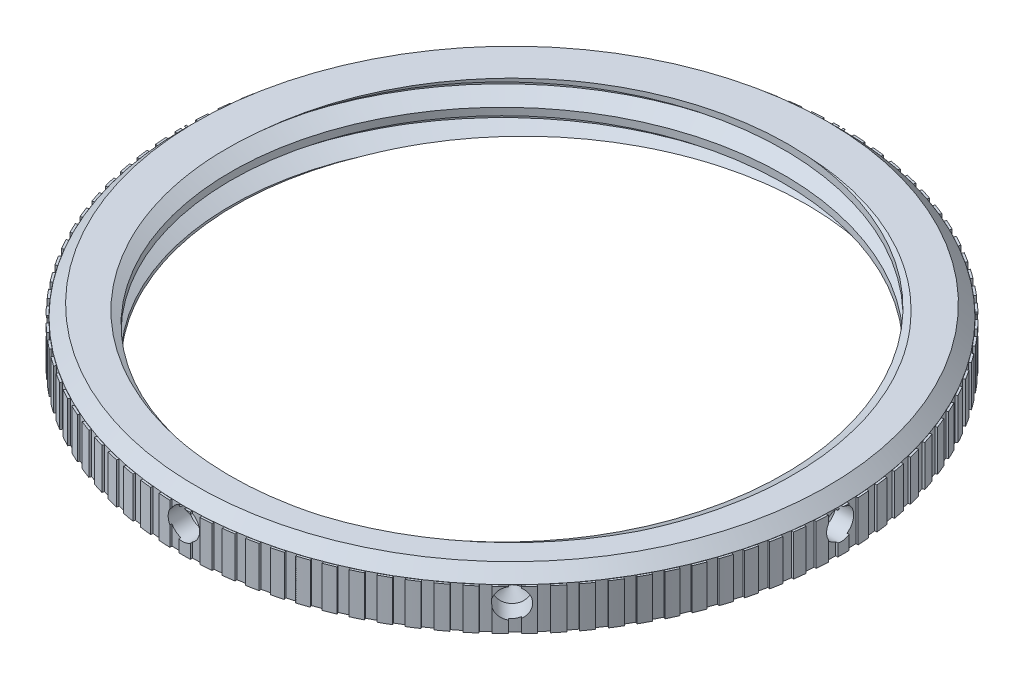
SolidWorks part; units mm, degrees
ref_plane "前视基准面" through (0, 0, 0) normal (0, 0, 1) x (1, 0, 0)
ref_plane "上视基准面" through (0, 0, 0) normal (0, 1, 0) x (1, 0, 0)
ref_plane "右视基准面" through (0, 0, 0) normal (1, 0, 0) x (0, 0, -1)
sketch "草图1" plane through (0, -4.5977, 0) normal (0, -1, 0) x (1, 0, 0)
  circle A0 centre (0, 0) radius 5
  circle A1 centre (0, 0) radius 5.6
  dimension "D1" = 10
  dimension "D2" = 11.2
extrude "凸台-拉伸1" add sketch "草图1" against normal blind 0.9 from surface at 0
chamfer "倒角2" distance 0.2 angle 45 1 edges at (0, -3.6977, -5.6)
thread "螺纹线1" pitch 0.5 start angle 0, offset 1, length 0, pitch 0.5, diameter 10
ref_plane "基准面4" through (5, -5.5977, 0) normal (0, 0, 1) x (1, 0, 0)
sketch "螺纹线轮廓1" plane through (5, -5.5977, 0) normal (0, 0, 1) x (1, 0, 0)
  line L0 (0, 0) -> (0, 0.5) construction
  line L11 (0, 0) -> (0, 0.4375)
  line L12 (0, 0.4375) -> (-0.2706, 0.2812)
  line L13 (-0.2706, 0.2812) -> (-0.2706, 0.1562)
  line L15 (-0.2706, 0.1562) -> (0, 0)
  line L17 (-0.2706, 0.2187) -> (0, 0.2187) construction
  point P2 (0, 0)
  dimension "Pitch" = 0.5
  dimension "Profile_Angle" = 60
  dimension "Profile_Land" = 0.125
  dimension "Profile_Height" = 0.2706
sketch "草图5" plane through (0, -4.5977, 0) normal (0, -1, 0) x (1, 0, 0)
  line L0 (0, 0) -> (3.2613, 4.5973) construction
  line L1 (0, 0) -> (3.7298, 4.8868) construction
  line L2 (3.1882, 4.4943) -> (3.3411, 4.3776)
  line L3 (3.3411, 4.3776) -> (3.4198, 4.4807)
  line L4 (3.2613, 4.5973) -> (3.1882, 4.4943)
  line L5 (2.9662, 4.793) -> (2.8997, 4.6856)
  line L6 (3.0596, 4.5787) -> (3.1317, 4.6866)
  line L7 (2.8997, 4.6856) -> (3.0596, 4.5787)
  line L8 (2.6594, 4.9698) -> (2.5998, 4.8584)
  line L9 (2.7661, 4.7618) -> (2.8312, 4.874)
  line L10 (2.5998, 4.8584) -> (2.7661, 4.7618)
  line L11 (2.3421, 5.127) -> (2.2896, 5.0121)
  line L12 (2.4616, 4.9261) -> (2.5196, 5.0421)
  line L13 (2.2896, 5.0121) -> (2.4616, 4.9261)
  line L14 (2.0156, 5.264) -> (1.9704, 5.1459)
  line L15 (2.1475, 5.071) -> (2.198, 5.1904)
  line L16 (1.9704, 5.1459) -> (2.1475, 5.071)
  line L17 (1.6811, 5.3801) -> (1.6434, 5.2595)
  line L18 (1.8248, 5.1958) -> (1.8678, 5.3182)
  line L19 (1.6434, 5.2595) -> (1.8248, 5.1958)
  line L20 (1.3399, 5.4751) -> (1.3099, 5.3523)
  line L21 (1.495, 5.3001) -> (1.5302, 5.425)
  line L22 (1.3099, 5.3523) -> (1.495, 5.3001)
  line L23 (0.9935, 5.5484) -> (0.9712, 5.424)
  line L24 (1.1592, 5.3835) -> (1.1865, 5.5103)
  line L25 (0.9712, 5.424) -> (1.1592, 5.3835)
  line L26 (0.6431, 5.5998) -> (0.6287, 5.4743)
  line L27 (0.8189, 5.4457) -> (0.8382, 5.574)
  line L28 (0.6287, 5.4743) -> (0.8189, 5.4457)
  line L29 (0.2903, 5.6292) -> (0.2838, 5.503)
  line L30 (0.4753, 5.4864) -> (0.4865, 5.6156)
  line L31 (0.2838, 5.503) -> (0.4753, 5.4864)
  line L32 (-0.0638, 5.6363) -> (-0.0623, 5.5099)
  line L33 (0.1299, 5.5054) -> (0.133, 5.6351)
  line L34 (-0.0623, 5.5099) -> (0.1299, 5.5054)
  line L35 (-0.4175, 5.6212) -> (-0.4082, 5.4951)
  line L36 (-0.216, 5.5027) -> (-0.2211, 5.6323)
  line L37 (-0.4082, 5.4951) -> (-0.216, 5.5027)
  line L38 (-0.7697, 5.5838) -> (-0.7524, 5.4587)
  line L39 (-0.5611, 5.4783) -> (-0.5743, 5.6073)
  line L40 (-0.7524, 5.4587) -> (-0.5611, 5.4783)
  line L41 (-1.1188, 5.5245) -> (-1.0937, 5.4007)
  line L42 (-0.904, 5.4322) -> (-0.9253, 5.5602)
  line L43 (-1.0937, 5.4007) -> (-0.904, 5.4322)
  line L44 (-1.4635, 5.4433) -> (-1.4306, 5.3213)
  line L45 (-1.2433, 5.3647) -> (-1.2726, 5.4911)
  line L46 (-1.4306, 5.3213) -> (-1.2433, 5.3647)
  line L47 (-1.8024, 5.3407) -> (-1.7619, 5.221)
  line L48 (-1.5777, 5.2761) -> (-1.6149, 5.4004)
  line L49 (-1.7619, 5.221) -> (-1.5777, 5.2761)
  line L50 (-2.1341, 5.217) -> (-2.0863, 5.1001)
  line L51 (-1.9059, 5.1666) -> (-1.9508, 5.2883)
  line L52 (-2.0863, 5.1001) -> (-1.9059, 5.1666)
  line L53 (-2.4575, 5.0727) -> (-2.4024, 4.959)
  line L54 (-2.2265, 5.0367) -> (-2.279, 5.1554)
  line L55 (-2.4024, 4.959) -> (-2.2265, 5.0367)
  line L56 (-2.7712, 4.9084) -> (-2.7091, 4.7984)
  line L57 (-2.5384, 4.887) -> (-2.5982, 5.0021)
  line L58 (-2.7091, 4.7984) -> (-2.5384, 4.887)
  line L59 (-3.0739, 4.7247) -> (-3.005, 4.6188)
  line L60 (-2.8402, 4.718) -> (-2.9071, 4.8291)
  line L61 (-3.005, 4.6188) -> (-2.8402, 4.718)
  line L62 (-3.3645, 4.5224) -> (-3.2891, 4.421)
  line L63 (-3.1309, 4.5303) -> (-3.2046, 4.637)
  line L64 (-3.2891, 4.421) -> (-3.1309, 4.5303)
  line L65 (-3.6418, 4.3022) -> (-3.5602, 4.2057)
  line L66 (-3.4092, 4.3248) -> (-3.4895, 4.4267)
  line L67 (-3.5602, 4.2057) -> (-3.4092, 4.3248)
  line L68 (-3.9048, 4.065) -> (-3.8172, 3.9739)
  line L69 (-3.674, 4.1022) -> (-3.7605, 4.1988)
  line L70 (-3.8172, 3.9739) -> (-3.674, 4.1022)
  line L71 (-4.1523, 3.8118) -> (-4.0592, 3.7264)
  line L72 (-3.9243, 3.8634) -> (-4.0168, 3.9544)
  line L73 (-4.0592, 3.7264) -> (-3.9243, 3.8634)
  line L74 (-4.3835, 3.5436) -> (-4.2852, 3.4641)
  line L75 (-4.1592, 3.6094) -> (-4.2571, 3.6944)
  line L76 (-4.2852, 3.4641) -> (-4.1592, 3.6094)
  line L77 (-4.5973, 3.2613) -> (-4.4943, 3.1882)
  line L78 (-4.3776, 3.3411) -> (-4.4807, 3.4198)
  line L79 (-4.4943, 3.1882) -> (-4.3776, 3.3411)
  line L80 (-4.793, 2.9662) -> (-4.6856, 2.8997)
  line L81 (-4.5787, 3.0596) -> (-4.6866, 3.1317)
  line L82 (-4.6856, 2.8997) -> (-4.5787, 3.0596)
  line L83 (-4.9698, 2.6594) -> (-4.8584, 2.5998)
  line L84 (-4.7618, 2.7661) -> (-4.874, 2.8312)
  line L85 (-4.8584, 2.5998) -> (-4.7618, 2.7661)
  line L86 (-5.127, 2.3421) -> (-5.0121, 2.2896)
  line L87 (-4.9261, 2.4616) -> (-5.0421, 2.5196)
  line L88 (-5.0121, 2.2896) -> (-4.9261, 2.4616)
  line L89 (-5.264, 2.0156) -> (-5.1459, 1.9704)
  line L90 (-5.071, 2.1475) -> (-5.1904, 2.198)
  line L91 (-5.1459, 1.9704) -> (-5.071, 2.1475)
  line L92 (-5.3801, 1.6811) -> (-5.2595, 1.6434)
  line L93 (-5.1958, 1.8248) -> (-5.3182, 1.8678)
  line L94 (-5.2595, 1.6434) -> (-5.1958, 1.8248)
  line L95 (-5.4751, 1.3399) -> (-5.3523, 1.3099)
  line L96 (-5.3001, 1.495) -> (-5.425, 1.5302)
  line L97 (-5.3523, 1.3099) -> (-5.3001, 1.495)
  line L98 (-5.5484, 0.9935) -> (-5.424, 0.9712)
  line L99 (-5.3835, 1.1592) -> (-5.5103, 1.1865)
  line L100 (-5.424, 0.9712) -> (-5.3835, 1.1592)
  line L101 (-5.5998, 0.6431) -> (-5.4743, 0.6287)
  line L102 (-5.4457, 0.8189) -> (-5.574, 0.8382)
  line L103 (-5.4743, 0.6287) -> (-5.4457, 0.8189)
  line L104 (-5.6292, 0.2903) -> (-5.503, 0.2838)
  line L105 (-5.4864, 0.4753) -> (-5.6156, 0.4865)
  line L106 (-5.503, 0.2838) -> (-5.4864, 0.4753)
  line L107 (-5.6363, -0.0638) -> (-5.5099, -0.0623)
  line L108 (-5.5054, 0.1299) -> (-5.6351, 0.133)
  line L109 (-5.5099, -0.0623) -> (-5.5054, 0.1299)
  line L110 (-5.6212, -0.4175) -> (-5.4951, -0.4082)
  line L111 (-5.5027, -0.216) -> (-5.6323, -0.2211)
  line L112 (-5.4951, -0.4082) -> (-5.5027, -0.216)
  line L113 (-5.5838, -0.7697) -> (-5.4587, -0.7524)
  line L114 (-5.4783, -0.5611) -> (-5.6073, -0.5743)
  line L115 (-5.4587, -0.7524) -> (-5.4783, -0.5611)
  line L116 (-5.5245, -1.1188) -> (-5.4007, -1.0937)
  line L117 (-5.4322, -0.904) -> (-5.5602, -0.9253)
  line L118 (-5.4007, -1.0937) -> (-5.4322, -0.904)
  line L119 (-5.4433, -1.4635) -> (-5.3213, -1.4306)
  line L120 (-5.3647, -1.2433) -> (-5.4911, -1.2726)
  line L121 (-5.3213, -1.4306) -> (-5.3647, -1.2433)
  line L122 (-5.3407, -1.8024) -> (-5.221, -1.7619)
  line L123 (-5.2761, -1.5777) -> (-5.4004, -1.6149)
  line L124 (-5.221, -1.7619) -> (-5.2761, -1.5777)
  line L125 (-5.217, -2.1341) -> (-5.1001, -2.0863)
  line L126 (-5.1666, -1.9059) -> (-5.2883, -1.9508)
  line L127 (-5.1001, -2.0863) -> (-5.1666, -1.9059)
  line L128 (-5.0727, -2.4575) -> (-4.959, -2.4024)
  line L129 (-5.0367, -2.2265) -> (-5.1554, -2.279)
  line L130 (-4.959, -2.4024) -> (-5.0367, -2.2265)
  line L131 (-4.9084, -2.7712) -> (-4.7984, -2.7091)
  line L132 (-4.887, -2.5384) -> (-5.0021, -2.5982)
  line L133 (-4.7984, -2.7091) -> (-4.887, -2.5384)
  line L134 (-4.7247, -3.0739) -> (-4.6188, -3.005)
  line L135 (-4.718, -2.8402) -> (-4.8291, -2.9071)
  line L136 (-4.6188, -3.005) -> (-4.718, -2.8402)
  line L137 (-4.5224, -3.3645) -> (-4.421, -3.2891)
  line L138 (-4.5303, -3.1309) -> (-4.637, -3.2046)
  line L139 (-4.421, -3.2891) -> (-4.5303, -3.1309)
  line L140 (-4.3022, -3.6418) -> (-4.2057, -3.5602)
  line L141 (-4.3248, -3.4092) -> (-4.4267, -3.4895)
  line L142 (-4.2057, -3.5602) -> (-4.3248, -3.4092)
  line L143 (-4.065, -3.9048) -> (-3.9739, -3.8172)
  line L144 (-4.1022, -3.674) -> (-4.1988, -3.7605)
  line L145 (-3.9739, -3.8172) -> (-4.1022, -3.674)
  line L146 (-3.8118, -4.1523) -> (-3.7264, -4.0592)
  line L147 (-3.8634, -3.9243) -> (-3.9544, -4.0168)
  line L148 (-3.7264, -4.0592) -> (-3.8634, -3.9243)
  line L149 (-3.5436, -4.3835) -> (-3.4641, -4.2852)
  line L150 (-3.6094, -4.1592) -> (-3.6944, -4.2571)
  line L151 (-3.4641, -4.2852) -> (-3.6094, -4.1592)
  line L152 (-3.2613, -4.5973) -> (-3.1882, -4.4943)
  line L153 (-3.3411, -4.3776) -> (-3.4198, -4.4807)
  line L154 (-3.1882, -4.4943) -> (-3.3411, -4.3776)
  line L155 (-2.9662, -4.793) -> (-2.8997, -4.6856)
  line L156 (-3.0596, -4.5787) -> (-3.1317, -4.6866)
  line L157 (-2.8997, -4.6856) -> (-3.0596, -4.5787)
  line L158 (-2.6594, -4.9698) -> (-2.5998, -4.8584)
  line L159 (-2.7661, -4.7618) -> (-2.8312, -4.874)
  line L160 (-2.5998, -4.8584) -> (-2.7661, -4.7618)
  line L161 (-2.3421, -5.127) -> (-2.2896, -5.0121)
  line L162 (-2.4616, -4.9261) -> (-2.5196, -5.0421)
  line L163 (-2.2896, -5.0121) -> (-2.4616, -4.9261)
  line L164 (-2.0156, -5.264) -> (-1.9704, -5.1459)
  line L165 (-2.1475, -5.071) -> (-2.198, -5.1904)
  line L166 (-1.9704, -5.1459) -> (-2.1475, -5.071)
  line L167 (-1.6811, -5.3801) -> (-1.6434, -5.2595)
  line L168 (-1.8248, -5.1958) -> (-1.8678, -5.3182)
  line L169 (-1.6434, -5.2595) -> (-1.8248, -5.1958)
  line L170 (-1.3399, -5.4751) -> (-1.3099, -5.3523)
  line L171 (-1.495, -5.3001) -> (-1.5302, -5.425)
  line L172 (-1.3099, -5.3523) -> (-1.495, -5.3001)
  line L173 (-0.9935, -5.5484) -> (-0.9712, -5.424)
  line L174 (-1.1592, -5.3835) -> (-1.1865, -5.5103)
  line L175 (-0.9712, -5.424) -> (-1.1592, -5.3835)
  line L176 (-0.6431, -5.5998) -> (-0.6287, -5.4743)
  line L177 (-0.8189, -5.4457) -> (-0.8382, -5.574)
  line L178 (-0.6287, -5.4743) -> (-0.8189, -5.4457)
  line L179 (-0.2903, -5.6292) -> (-0.2838, -5.503)
  line L180 (-0.4753, -5.4864) -> (-0.4865, -5.6156)
  line L181 (-0.2838, -5.503) -> (-0.4753, -5.4864)
  line L182 (0.0638, -5.6363) -> (0.0623, -5.5099)
  line L183 (-0.1299, -5.5054) -> (-0.133, -5.6351)
  line L184 (0.0623, -5.5099) -> (-0.1299, -5.5054)
  line L185 (0.4175, -5.6212) -> (0.4082, -5.4951)
  line L186 (0.216, -5.5027) -> (0.2211, -5.6323)
  line L187 (0.4082, -5.4951) -> (0.216, -5.5027)
  line L188 (0.7697, -5.5838) -> (0.7524, -5.4587)
  line L189 (0.5611, -5.4783) -> (0.5743, -5.6073)
  line L190 (0.7524, -5.4587) -> (0.5611, -5.4783)
  line L191 (1.1188, -5.5245) -> (1.0937, -5.4007)
  line L192 (0.904, -5.4322) -> (0.9253, -5.5602)
  line L193 (1.0937, -5.4007) -> (0.904, -5.4322)
  line L194 (1.4635, -5.4433) -> (1.4306, -5.3213)
  line L195 (1.2433, -5.3647) -> (1.2726, -5.4911)
  line L196 (1.4306, -5.3213) -> (1.2433, -5.3647)
  line L197 (1.8024, -5.3407) -> (1.7619, -5.221)
  line L198 (1.5777, -5.2761) -> (1.6149, -5.4004)
  line L199 (1.7619, -5.221) -> (1.5777, -5.2761)
  line L200 (2.1341, -5.217) -> (2.0863, -5.1001)
  line L201 (1.9059, -5.1666) -> (1.9508, -5.2883)
  line L202 (2.0863, -5.1001) -> (1.9059, -5.1666)
  line L203 (2.4575, -5.0727) -> (2.4024, -4.959)
  line L204 (2.2265, -5.0367) -> (2.279, -5.1554)
  line L205 (2.4024, -4.959) -> (2.2265, -5.0367)
  line L206 (2.7712, -4.9084) -> (2.7091, -4.7984)
  line L207 (2.5384, -4.887) -> (2.5982, -5.0021)
  line L208 (2.7091, -4.7984) -> (2.5384, -4.887)
  line L209 (3.0739, -4.7247) -> (3.005, -4.6188)
  line L210 (2.8402, -4.718) -> (2.9071, -4.8291)
  line L211 (3.005, -4.6188) -> (2.8402, -4.718)
  line L212 (3.3645, -4.5224) -> (3.2891, -4.421)
  line L213 (3.1309, -4.5303) -> (3.2046, -4.637)
  line L214 (3.2891, -4.421) -> (3.1309, -4.5303)
  line L215 (3.6418, -4.3022) -> (3.5602, -4.2057)
  line L216 (3.4092, -4.3248) -> (3.4895, -4.4267)
  line L217 (3.5602, -4.2057) -> (3.4092, -4.3248)
  line L218 (3.9048, -4.065) -> (3.8172, -3.9739)
  line L219 (3.674, -4.1022) -> (3.7605, -4.1988)
  line L220 (3.8172, -3.9739) -> (3.674, -4.1022)
  line L221 (4.1523, -3.8118) -> (4.0592, -3.7264)
  line L222 (3.9243, -3.8634) -> (4.0168, -3.9544)
  line L223 (4.0592, -3.7264) -> (3.9243, -3.8634)
  line L224 (4.3835, -3.5436) -> (4.2852, -3.4641)
  line L225 (4.1592, -3.6094) -> (4.2571, -3.6944)
  line L226 (4.2852, -3.4641) -> (4.1592, -3.6094)
  line L227 (4.5973, -3.2613) -> (4.4943, -3.1882)
  line L228 (4.3776, -3.3411) -> (4.4807, -3.4198)
  line L229 (4.4943, -3.1882) -> (4.3776, -3.3411)
  line L230 (4.793, -2.9662) -> (4.6856, -2.8997)
  line L231 (4.5787, -3.0596) -> (4.6866, -3.1317)
  line L232 (4.6856, -2.8997) -> (4.5787, -3.0596)
  line L233 (4.9698, -2.6594) -> (4.8584, -2.5998)
  line L234 (4.7618, -2.7661) -> (4.874, -2.8312)
  line L235 (4.8584, -2.5998) -> (4.7618, -2.7661)
  line L236 (5.127, -2.3421) -> (5.0121, -2.2896)
  line L237 (4.9261, -2.4616) -> (5.0421, -2.5196)
  line L238 (5.0121, -2.2896) -> (4.9261, -2.4616)
  line L239 (5.264, -2.0156) -> (5.1459, -1.9704)
  line L240 (5.071, -2.1475) -> (5.1904, -2.198)
  line L241 (5.1459, -1.9704) -> (5.071, -2.1475)
  line L242 (5.3801, -1.6811) -> (5.2595, -1.6434)
  line L243 (5.1958, -1.8248) -> (5.3182, -1.8678)
  line L244 (5.2595, -1.6434) -> (5.1958, -1.8248)
  line L245 (5.4751, -1.3399) -> (5.3523, -1.3099)
  line L246 (5.3001, -1.495) -> (5.425, -1.5302)
  line L247 (5.3523, -1.3099) -> (5.3001, -1.495)
  line L248 (5.5484, -0.9935) -> (5.424, -0.9712)
  line L249 (5.3835, -1.1592) -> (5.5103, -1.1865)
  line L250 (5.424, -0.9712) -> (5.3835, -1.1592)
  line L251 (5.5998, -0.6431) -> (5.4743, -0.6287)
  line L252 (5.4457, -0.8189) -> (5.574, -0.8382)
  line L253 (5.4743, -0.6287) -> (5.4457, -0.8189)
  line L254 (5.6292, -0.2903) -> (5.503, -0.2838)
  line L255 (5.4864, -0.4753) -> (5.6156, -0.4865)
  line L256 (5.503, -0.2838) -> (5.4864, -0.4753)
  line L257 (5.6363, 0.0638) -> (5.5099, 0.0623)
  line L258 (5.5054, -0.1299) -> (5.6351, -0.133)
  line L259 (5.5099, 0.0623) -> (5.5054, -0.1299)
  line L260 (5.6212, 0.4175) -> (5.4951, 0.4082)
  line L261 (5.5027, 0.216) -> (5.6323, 0.2211)
  line L262 (5.4951, 0.4082) -> (5.5027, 0.216)
  line L263 (5.5838, 0.7697) -> (5.4587, 0.7524)
  line L264 (5.4783, 0.5611) -> (5.6073, 0.5743)
  line L265 (5.4587, 0.7524) -> (5.4783, 0.5611)
  line L266 (5.5245, 1.1188) -> (5.4007, 1.0937)
  line L267 (5.4322, 0.904) -> (5.5602, 0.9253)
  line L268 (5.4007, 1.0937) -> (5.4322, 0.904)
  line L269 (5.4433, 1.4635) -> (5.3213, 1.4306)
  line L270 (5.3647, 1.2433) -> (5.4911, 1.2726)
  line L271 (5.3213, 1.4306) -> (5.3647, 1.2433)
  line L272 (5.3407, 1.8024) -> (5.221, 1.7619)
  line L273 (5.2761, 1.5777) -> (5.4004, 1.6149)
  line L274 (5.221, 1.7619) -> (5.2761, 1.5777)
  line L275 (5.217, 2.1341) -> (5.1001, 2.0863)
  line L276 (5.1666, 1.9059) -> (5.2883, 1.9508)
  line L277 (5.1001, 2.0863) -> (5.1666, 1.9059)
  line L278 (5.0727, 2.4575) -> (4.959, 2.4024)
  line L279 (5.0367, 2.2265) -> (5.1554, 2.279)
  line L280 (4.959, 2.4024) -> (5.0367, 2.2265)
  line L281 (4.9084, 2.7712) -> (4.7984, 2.7091)
  line L282 (4.887, 2.5384) -> (5.0021, 2.5982)
  line L283 (4.7984, 2.7091) -> (4.887, 2.5384)
  line L284 (4.7247, 3.0739) -> (4.6188, 3.005)
  line L285 (4.718, 2.8402) -> (4.8291, 2.9071)
  line L286 (4.6188, 3.005) -> (4.718, 2.8402)
  line L287 (4.5224, 3.3645) -> (4.421, 3.2891)
  line L288 (4.5303, 3.1309) -> (4.637, 3.2046)
  line L289 (4.421, 3.2891) -> (4.5303, 3.1309)
  line L290 (4.3022, 3.6418) -> (4.2057, 3.5602)
  line L291 (4.3248, 3.4092) -> (4.4267, 3.4895)
  line L292 (4.2057, 3.5602) -> (4.3248, 3.4092)
  line L293 (4.065, 3.9048) -> (3.9739, 3.8172)
  line L294 (4.1022, 3.674) -> (4.1988, 3.7605)
  line L295 (3.9739, 3.8172) -> (4.1022, 3.674)
  line L296 (3.8118, 4.1523) -> (3.7264, 4.0592)
  line L297 (3.8634, 3.9243) -> (3.9544, 4.0168)
  line L298 (3.7264, 4.0592) -> (3.8634, 3.9243)
  line L299 (3.5436, 4.3835) -> (3.4641, 4.2852)
  line L300 (3.6094, 4.1592) -> (3.6944, 4.2571)
  line L301 (3.4641, 4.2852) -> (3.6094, 4.1592)
  arc A0 (3.2613, 4.5973) -> (3.4198, 4.4807) centre (0, 0) cw
  arc A1 (2.9662, 4.793) -> (3.1317, 4.6866) centre (0, 0) cw
  arc A2 (2.6594, 4.9698) -> (2.8312, 4.874) centre (0, 0) cw
  arc A3 (2.3421, 5.127) -> (2.5196, 5.0421) centre (0, 0) cw
  arc A4 (2.0156, 5.264) -> (2.198, 5.1904) centre (0, 0) cw
  arc A5 (1.6811, 5.3801) -> (1.8678, 5.3182) centre (0, 0) cw
  arc A6 (1.3399, 5.4751) -> (1.5302, 5.425) centre (0, 0) cw
  arc A7 (0.9935, 5.5484) -> (1.1865, 5.5103) centre (0, 0) cw
  arc A8 (0.6431, 5.5998) -> (0.8382, 5.574) centre (0, 0) cw
  arc A9 (0.2903, 5.6292) -> (0.4865, 5.6156) centre (0, 0) cw
  arc A10 (-0.0638, 5.6363) -> (0.133, 5.6351) centre (0, 0) cw
  arc A11 (-0.4175, 5.6212) -> (-0.2211, 5.6323) centre (0, 0) cw
  arc A12 (-0.7697, 5.5838) -> (-0.5743, 5.6073) centre (0, 0) cw
  arc A13 (-1.1188, 5.5245) -> (-0.9253, 5.5602) centre (0, 0) cw
  arc A14 (-1.4635, 5.4433) -> (-1.2726, 5.4911) centre (0, 0) cw
  arc A15 (-1.8024, 5.3407) -> (-1.6149, 5.4004) centre (0, 0) cw
  arc A16 (-2.1341, 5.217) -> (-1.9508, 5.2883) centre (0, 0) cw
  arc A17 (-2.4575, 5.0727) -> (-2.279, 5.1554) centre (0, 0) cw
  arc A18 (-2.7712, 4.9084) -> (-2.5982, 5.0021) centre (0, 0) cw
  arc A19 (-3.0739, 4.7247) -> (-2.9071, 4.8291) centre (0, 0) cw
  arc A20 (-3.3645, 4.5224) -> (-3.2046, 4.637) centre (0, 0) cw
  arc A21 (-3.6418, 4.3022) -> (-3.4895, 4.4267) centre (0, 0) cw
  arc A22 (-3.9048, 4.065) -> (-3.7605, 4.1988) centre (0, 0) cw
  arc A23 (-4.1523, 3.8118) -> (-4.0168, 3.9544) centre (0, 0) cw
  arc A24 (-4.3835, 3.5436) -> (-4.2571, 3.6944) centre (0, 0) cw
  arc A25 (-4.5973, 3.2613) -> (-4.4807, 3.4198) centre (0, 0) cw
  arc A26 (-4.793, 2.9662) -> (-4.6866, 3.1317) centre (0, 0) cw
  arc A27 (-4.9698, 2.6594) -> (-4.874, 2.8312) centre (0, 0) cw
  arc A28 (-5.127, 2.3421) -> (-5.0421, 2.5196) centre (0, 0) cw
  arc A29 (-5.264, 2.0156) -> (-5.1904, 2.198) centre (0, 0) cw
  arc A30 (-5.3801, 1.6811) -> (-5.3182, 1.8678) centre (0, 0) cw
  arc A31 (-5.4751, 1.3399) -> (-5.425, 1.5302) centre (0, 0) cw
  arc A32 (-5.5484, 0.9935) -> (-5.5103, 1.1865) centre (0, 0) cw
  arc A33 (-5.5998, 0.6431) -> (-5.574, 0.8382) centre (0, 0) cw
  arc A34 (-5.6292, 0.2903) -> (-5.6156, 0.4865) centre (0, 0) cw
  arc A35 (-5.6363, -0.0638) -> (-5.6351, 0.133) centre (0, 0) cw
  arc A36 (-5.6212, -0.4175) -> (-5.6323, -0.2211) centre (0, 0) cw
  arc A37 (-5.5838, -0.7697) -> (-5.6073, -0.5743) centre (0, 0) cw
  arc A38 (-5.5245, -1.1188) -> (-5.5602, -0.9253) centre (0, 0) cw
  arc A39 (-5.4433, -1.4635) -> (-5.4911, -1.2726) centre (0, 0) cw
  arc A40 (-5.3407, -1.8024) -> (-5.4004, -1.6149) centre (0, 0) cw
  arc A41 (-5.217, -2.1341) -> (-5.2883, -1.9508) centre (0, 0) cw
  arc A42 (-5.0727, -2.4575) -> (-5.1554, -2.279) centre (0, 0) cw
  arc A43 (-4.9084, -2.7712) -> (-5.0021, -2.5982) centre (0, 0) cw
  arc A44 (-4.7247, -3.0739) -> (-4.8291, -2.9071) centre (0, 0) cw
  arc A45 (-4.5224, -3.3645) -> (-4.637, -3.2046) centre (0, 0) cw
  arc A46 (-4.3022, -3.6418) -> (-4.4267, -3.4895) centre (0, 0) cw
  arc A47 (-4.065, -3.9048) -> (-4.1988, -3.7605) centre (0, 0) cw
  arc A48 (-3.8118, -4.1523) -> (-3.9544, -4.0168) centre (0, 0) cw
  arc A49 (-3.5436, -4.3835) -> (-3.6944, -4.2571) centre (0, 0) cw
  arc A50 (-3.2613, -4.5973) -> (-3.4198, -4.4807) centre (0, 0) cw
  arc A51 (-2.9662, -4.793) -> (-3.1317, -4.6866) centre (0, 0) cw
  arc A52 (-2.6594, -4.9698) -> (-2.8312, -4.874) centre (0, 0) cw
  arc A53 (-2.3421, -5.127) -> (-2.5196, -5.0421) centre (0, 0) cw
  arc A54 (-2.0156, -5.264) -> (-2.198, -5.1904) centre (0, 0) cw
  arc A55 (-1.6811, -5.3801) -> (-1.8678, -5.3182) centre (0, 0) cw
  arc A56 (-1.3399, -5.4751) -> (-1.5302, -5.425) centre (0, 0) cw
  arc A57 (-0.9935, -5.5484) -> (-1.1865, -5.5103) centre (0, 0) cw
  arc A58 (-0.6431, -5.5998) -> (-0.8382, -5.574) centre (0, 0) cw
  arc A59 (-0.2903, -5.6292) -> (-0.4865, -5.6156) centre (0, 0) cw
  arc A60 (0.0638, -5.6363) -> (-0.133, -5.6351) centre (0, 0) cw
  arc A61 (0.4175, -5.6212) -> (0.2211, -5.6323) centre (0, 0) cw
  arc A62 (0.7697, -5.5838) -> (0.5743, -5.6073) centre (0, 0) cw
  arc A63 (1.1188, -5.5245) -> (0.9253, -5.5602) centre (0, 0) cw
  arc A64 (1.4635, -5.4433) -> (1.2726, -5.4911) centre (0, 0) cw
  arc A65 (1.8024, -5.3407) -> (1.6149, -5.4004) centre (0, 0) cw
  arc A66 (2.1341, -5.217) -> (1.9508, -5.2883) centre (0, 0) cw
  arc A67 (2.4575, -5.0727) -> (2.279, -5.1554) centre (0, 0) cw
  arc A68 (2.7712, -4.9084) -> (2.5982, -5.0021) centre (0, 0) cw
  arc A69 (3.0739, -4.7247) -> (2.9071, -4.8291) centre (0, 0) cw
  arc A70 (3.3645, -4.5224) -> (3.2046, -4.637) centre (0, 0) cw
  arc A71 (3.6418, -4.3022) -> (3.4895, -4.4267) centre (0, 0) cw
  arc A72 (3.9048, -4.065) -> (3.7605, -4.1988) centre (0, 0) cw
  arc A73 (4.1523, -3.8118) -> (4.0168, -3.9544) centre (0, 0) cw
  arc A74 (4.3835, -3.5436) -> (4.2571, -3.6944) centre (0, 0) cw
  arc A75 (4.5973, -3.2613) -> (4.4807, -3.4198) centre (0, 0) cw
  arc A76 (4.793, -2.9662) -> (4.6866, -3.1317) centre (0, 0) cw
  arc A77 (4.9698, -2.6594) -> (4.874, -2.8312) centre (0, 0) cw
  arc A78 (5.127, -2.3421) -> (5.0421, -2.5196) centre (0, 0) cw
  arc A79 (5.264, -2.0156) -> (5.1904, -2.198) centre (0, 0) cw
  arc A80 (5.3801, -1.6811) -> (5.3182, -1.8678) centre (0, 0) cw
  arc A81 (5.4751, -1.3399) -> (5.425, -1.5302) centre (0, 0) cw
  arc A82 (5.5484, -0.9935) -> (5.5103, -1.1865) centre (0, 0) cw
  arc A83 (5.5998, -0.6431) -> (5.574, -0.8382) centre (0, 0) cw
  arc A84 (5.6292, -0.2903) -> (5.6156, -0.4865) centre (0, 0) cw
  arc A85 (5.6363, 0.0638) -> (5.6351, -0.133) centre (0, 0) cw
  arc A86 (5.6212, 0.4175) -> (5.6323, 0.2211) centre (0, 0) cw
  arc A87 (5.5838, 0.7697) -> (5.6073, 0.5743) centre (0, 0) cw
  arc A88 (5.5245, 1.1188) -> (5.5602, 0.9253) centre (0, 0) cw
  arc A89 (5.4433, 1.4635) -> (5.4911, 1.2726) centre (0, 0) cw
  arc A90 (5.3407, 1.8024) -> (5.4004, 1.6149) centre (0, 0) cw
  arc A91 (5.217, 2.1341) -> (5.2883, 1.9508) centre (0, 0) cw
  arc A92 (5.0727, 2.4575) -> (5.1554, 2.279) centre (0, 0) cw
  arc A93 (4.9084, 2.7712) -> (5.0021, 2.5982) centre (0, 0) cw
  arc A94 (4.7247, 3.0739) -> (4.8291, 2.9071) centre (0, 0) cw
  arc A95 (4.5224, 3.3645) -> (4.637, 3.2046) centre (0, 0) cw
  arc A96 (4.3022, 3.6418) -> (4.4267, 3.4895) centre (0, 0) cw
  arc A97 (4.065, 3.9048) -> (4.1988, 3.7605) centre (0, 0) cw
  arc A98 (3.8118, 4.1523) -> (3.9544, 4.0168) centre (0, 0) cw
  arc A99 (3.5436, 4.3835) -> (3.6944, 4.2571) centre (0, 0) cw
  dimension "D1" = 2
  dimension "D2" = 100
extrude "凸台-拉伸2" add sketch "草图5" against normal blind 0.698
ref_plane "基准面5" through (0, 0, 5.6366) normal (0, 0, 1) x (1, 0, 0)
sketch "草图6" plane through (0, 0, 5.6366) normal (0, 0, 1) x (1, 0, 0)
  line L0 (0, 0) -> (0, -6.5874) construction
  line L3 (0.1321, -4.5977) -> (0.2884, -4.5977) construction
  circle A0 centre (0, -4.1477) radius 0.25
  point P0 (0, -4.1477)
  dimension "D1" = 0.5
  dimension "D2" = 0.45
ref_plane "基准面6" through (0, 0, -5.6366) normal (0, 0, -1) x (-1, 0, 0)
hole_wizard "Ø1.0mm 暗销孔1" positions "草图6" profile "草图8" hole size "Ø1.0" standard "JIS"
sketch "草图8" plane through (0, -4.1477, 5.6366) normal (1, 0, 0) x (0, -1, 0)
  line L0 (0, 0) -> (0, 0.5)
  line L1 (0, 0.5) -> (0.25, 0.3498)
  line L2 (0.25, 0.3498) -> (0.25, 0)
  line L5 (0.25, 0) -> (0, 0)
  line L10 (0, 0.5) -> (-0.25, 0.3498) construction
  line L11 (0, -6.35) -> (0, 107.95) construction
  dimension "孔直径" = 0.5
  dimension "孔深度" = 0.5
  dimension "导头角度" = 118
sketch "草图9" plane through (0, 0, 0) normal (0, 0, 1) x (1, 0, 0)
  line L0 (0, 0) -> (0, -5.9517) construction
pattern_circular "阵列(圆周)1" count 8 over 360 about axis through (0, 0, 0) along (0, -1, 0) of "Ø1.0mm 暗销孔1"
